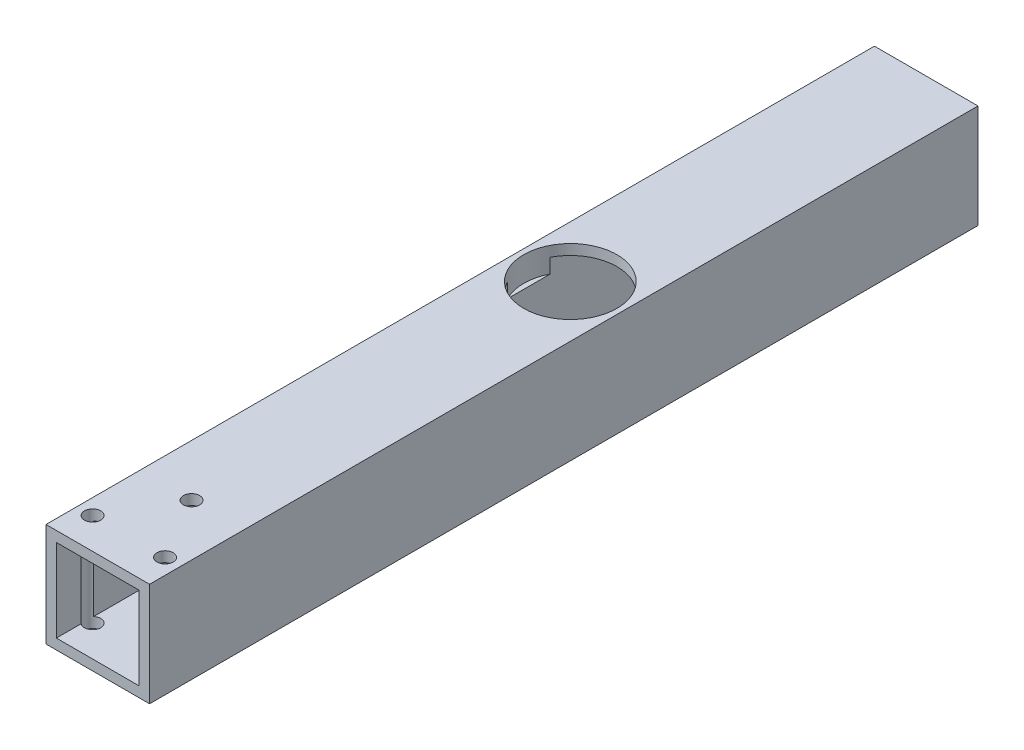
SolidWorks part; units mm, degrees
ref_plane "Front Plane" through (0, 0, 0) normal (0, 0, 1) x (1, 0, 0)
ref_plane "Top Plane" through (0, 0, 0) normal (0, 1, 0) x (1, 0, 0)
ref_plane "Right Plane" through (0, 0, 0) normal (1, 0, 0) x (0, 0, -1)
sketch "Sketch1" plane through (0, 0, 0) normal (0, 0, 1) x (1, 0, 0)
  line L0 (-12.7, 12.7) -> (12.7, 12.7)
  line L2 (-15.875, 15.875) -> (15.875, 15.875)
  line L3 (-15.875, 15.875) -> (-15.875, -15.875)
  line L4 (-15.875, -15.875) -> (15.875, -15.875)
  line L5 (15.875, 15.875) -> (15.875, -15.875)
  line L10 (12.7, 12.7) -> (12.7, -12.7)
  line L11 (-12.7, -12.7) -> (12.7, -12.7)
  line L12 (-12.7, 12.7) -> (-12.7, -12.7)
  point P12 (0, 15.875)
  point P14 (15.875, 0)
  dimension "Wall Thickness" = 3.175
  dimension "Outside Width" = 31.75
  dimension "Outside Height" = 31.75
  dimension "Inside Height" = 25.4
  dimension "Inside Width" = 25.4
sketch "Sketch2" plane through (0, 0, 0) normal (1, 0, 0) x (0, 0, -1)
  line L0 (127, 0) -> (-127, 0)
  point P4 (0, 0)
  point P7 (-127, 0)
  point P10 (127, 0)
  dimension "Length" = 254
sketch "Sketch3" plane through (0, 0, 0) normal (0, 0, 1) x (1, 0, 0)
  line L21 (15.875, 15.875) -> (-15.875, 15.875)
  line L22 (15.875, -15.875) -> (15.875, 15.875)
  line L23 (-15.875, -15.875) -> (15.875, -15.875)
  line L24 (-15.875, 15.875) -> (-15.875, -15.875)
  line L25 (15.875, 15.875) -> (-15.875, 15.875)
  line L26 (15.875, -15.875) -> (15.875, 15.875)
  line L27 (-15.875, -15.875) -> (15.875, -15.875)
  line L28 (-15.875, 15.875) -> (-15.875, -15.875)
  line L29 (12.7, 12.7) -> (-12.7, 12.7)
  line L30 (12.7, -12.7) -> (12.7, 12.7)
  line L31 (-12.7, -12.7) -> (12.7, -12.7)
  line L32 (-12.7, 12.7) -> (-12.7, -12.7)
  line L33 (12.7, 12.7) -> (-12.7, 12.7)
  line L34 (12.7, -12.7) -> (12.7, 12.7)
  line L35 (-12.7, -12.7) -> (12.7, -12.7)
  line L36 (-12.7, 12.7) -> (-12.7, -12.7)
  dimension "D1" = 0
  dimension "D2" = 0
extrude "Boss-Extrude1" add sketch "Sketch3" along normal up to vertex (127 mm away) and the other way up to vertex (127 mm away) up to point (0, 0, 127) other way up to point (0, 0, -127)
sketch "Drawing Reference" plane through (0, 0, 0) normal (1, 0, 0) x (0, 0, -1)
  line L0 (-127, 0) -> (127, 0) construction
  line L1 (0, -15.875) -> (0, 15.875) construction
  line L2 (-127, -15.875) -> (127, -15.875) construction
  line L5 (-127, 15.875) -> (127, 15.875) construction
  point P7 (-104.14, 0)
  point P8 (104.14, 0)
  dimension "D1" = 22.86
sketch "Sketch4" plane through (0, 15.875, 0) normal (0, 1, 0) x (1, 0, 0)
  line L0 (0, -127) -> (0, -117.475) construction
  line L1 (15.875, -127) -> (-15.875, -127) construction
  line L2 (0, -117.475) -> (11.1125, -117.475) construction
  line L3 (0, -117.475) -> (-11.1125, -117.475) construction
  line L4 (0, -117.475) -> (0, 17.8816) construction
  line L5 (0, -117.475) -> (0, -98.2472) construction
  dimension "D1" = 135.3566
  dimension "D2" = 22.225
  dimension "D3" = 9.525
hole_wizard "#10 Clearance Hole1" positions "Sketch5" profile "Sketch6" hole size "#10" standard "ANSI Inch" end condition through all
sketch "Sketch5" plane through (0, 15.875, 0) normal (0, 1, 0) x (1, 0, 0)
  point P0 (-11.1125, -117.475)
  point P3 (11.1125, -117.475)
  point P7 (0, -98.2472)
sketch "Sketch6" plane through (-11.1125, 15.875, 117.475) normal (1, 0, 0) x (0, 0, 1)
  line L0 (0, 0) -> (0, 31.75)
  line L1 (0, 31.75) -> (2.4892, 31.75)
  line L2 (2.4892, 31.75) -> (2.4892, 0)
  line L5 (2.4892, 0) -> (0, 0)
  line L11 (0, -6.35) -> (0, 107.95) construction
  dimension "Thru Hole Dia." = 4.9784
  dimension "Thru Hole Depth" = 31.75
sketch "Sketch7" plane through (0, 15.875, 0) normal (0, 1, 0) x (1, 0, 0)
  circle A0 centre (0, 17.8816) radius 14.2875
  dimension "D1" = 28.575
extrude "Cut-Extrude1" cut sketch "Sketch7" against normal blind 7.62
sketch "Sketch8" plane through (0, -15.875, 0) normal (0, -1, 0) x (1, 0, 0)
  circle A0 centre (0, -17.8816) radius 14.2875
  dimension "D1" = 28.575
extrude "Cut-Extrude2" cut sketch "Sketch8" against normal blind 7.62
equation "\"D1@Drawing Reference\"=\"Outside Width@Sketch1\" * 0.72"
